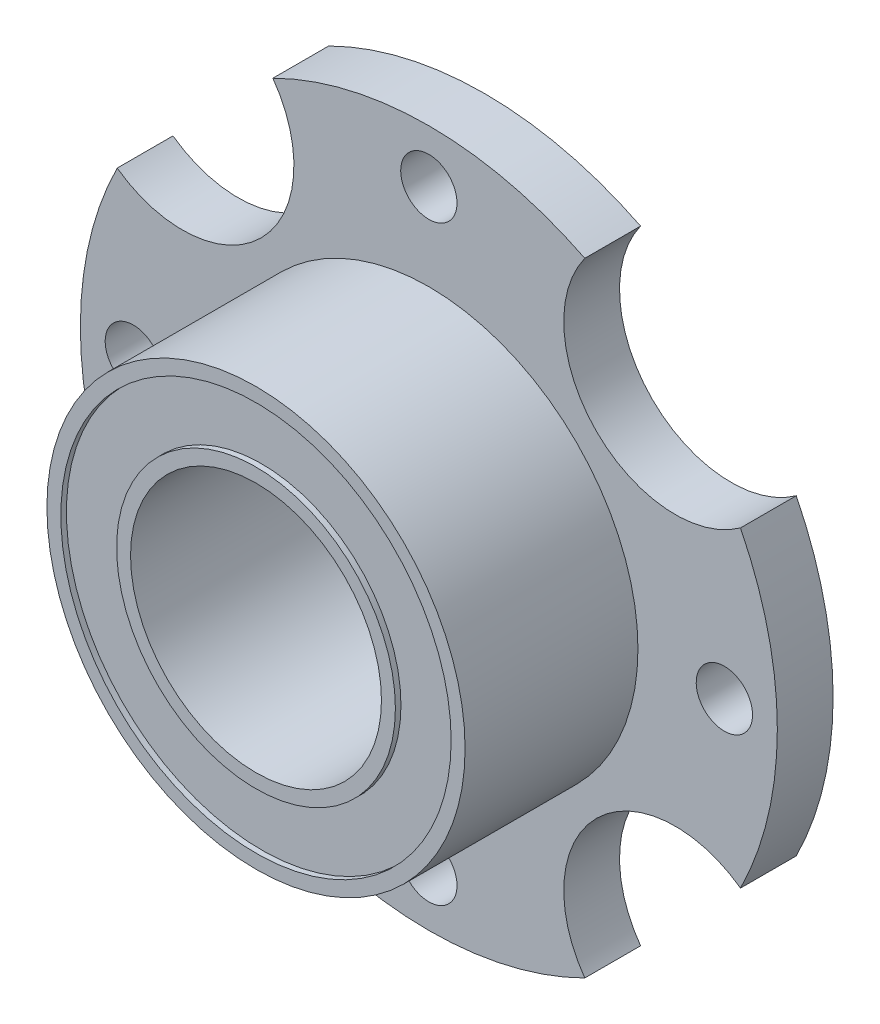
SolidWorks part; units mm, degrees
ref_plane "Płaszczyzna przednia" through (0, 0, 0) normal (0, 0, 1) x (1, 0, 0)
ref_plane "Płaszczyzna górna" through (0, 0, 0) normal (0, 1, 0) x (1, 0, 0)
ref_plane "Płaszczyzna prawa" through (0, 0, 0) normal (1, 0, 0) x (0, 0, -1)
sketch "Szkic1" plane through (0, 0, 0) normal (0, 0, 1) x (1, 0, 0)
  circle A0 centre (0, 0) radius 22.5
  circle A1 centre (0, 0) radius 37.5
  dimension "D1" = 75
  dimension "D2" = 45
extrude "Dodanie-wyciągnięcie1" add sketch "Szkic1" along normal blind 41
sketch "Szkic2" plane through (0, 0, 41) normal (0, 0, 1) x (1, 0, 0)
  circle A0 centre (0, 0) radius 25
  circle A1 centre (0, 0) radius 35
  dimension "D1" = 70
  dimension "D2" = 50
extrude "Wytnij-wyciągnięcie1" cut sketch "Szkic2" against normal blind 1
ref_plane "Płaszczyzna1" through (0, 0, 20.5) normal (0, 0, 1) x (1, 0, 0)
mirror "Lustro1" about plane through (0, 0, 20.5) normal (0, 0, 1) of "Wytnij-wyciągnięcie1"
sketch "Szkic3" plane through (0, 0, 0) normal (0, 0, 1) x (1, 0, 0)
  line L0 (0, 0) -> (-57.5571, -57.5571) construction
  line L1 (0, 0) -> (0, -75) construction
  circle A0 centre (0, -53) radius 5.05
  circle A1 centre (0, 0) radius 37.5
  circle A2 centre (0, 0) radius 37.5 construction
  arc A3 (-27.9715, -55.8914) -> (-55.8914, -27.9715) centre (0, 0) ccw
  arc A4 (-27.9715, -55.8914) -> (-55.8914, -27.9715) centre (-44.1942, -44.1942) ccw
  dimension "D1" = 10.1
  dimension "D3" = 125
  dimension "D5" = 40
  dimension "D2" = 53
  dimension "D4" = 45
  dimension "D6" = 62.5
extrude "Dodanie-wyciągnięcie2" add sketch "Szkic3" along normal blind 10
pattern_circular "Szyk kołowy1" count 4 every 90 about axis through (0, 0, 41) along (0, 0, 1) of face at (-35.9917, -35.9917, 5) of face at (5.05, -53, 10)
